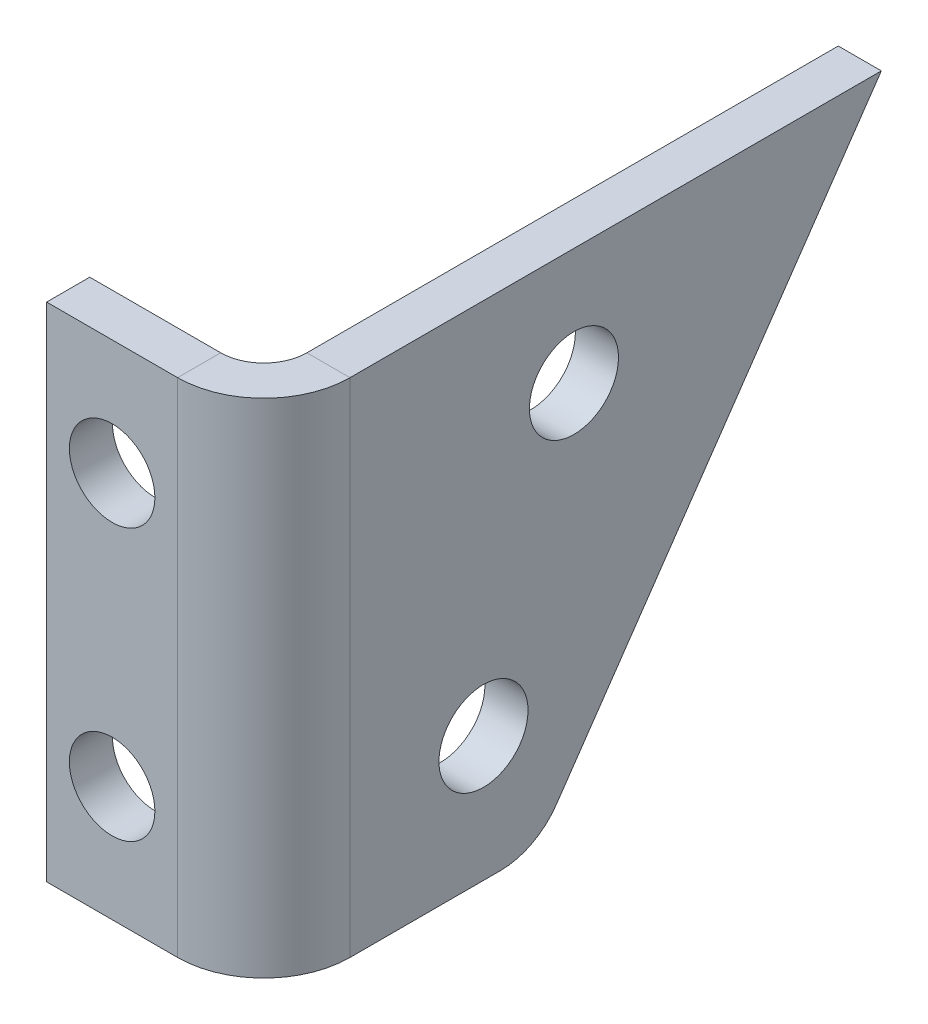
SolidWorks part; units mm, degrees
note: The reader was unsure of these and kept them because the rebuilt part matched: flange length of "Edge-Flange1".
ref_plane "Front Plane" through (0, 0, 0) normal (0, 0, 1) x (1, 0, 0)
ref_plane "Top Plane" through (0, 0, 0) normal (0, 1, 0) x (1, 0, 0)
ref_plane "Right Plane" through (0, 0, 0) normal (1, 0, 0) x (0, 0, -1)
sketch "Sketch1" plane through (0, 0, 0) normal (1, 0, 0) x (0, 0, -1)
  line L0 (71.7184, 2.1678) -> (102.9942, 47.6694)
  line L1 (0, 0) -> (95.6245, 0)
  line L5 (74.7808, 82.752) -> (14.6027, 58.2976)
  line L6 (11.5511, 53.6652) -> (11.5511, 40.2912)
  line L7 (11.5511, 40.2912) -> (48.3501, 40.2912)
  line L8 (50.1591, 38.5003) -> (50.1591, 0)
  line L9 (50.1591, 0) -> (67.5979, 0)
  line L10 (56.6677, 37) -> (96.5316, 37)
  line L11 (48.5511, 46.2861) -> (48.5511, 71.7841)
  arc A0 (67.5979, 0) -> (71.7184, 2.1678) centre (67.5979, 5) ccw
  arc A1 (102.9942, 47.6694) -> (74.7808, 82.752) centre (83.6279, 60.9809) ccw
  arc A2 (14.6027, 58.2976) -> (11.5511, 53.6652) centre (16.551, 53.6928) ccw
  arc A3 (50.1591, 38.5003) -> (48.3501, 40.2912) centre (48.3591, 38.4912) ccw
  circle A4 centre (20.4902, 52.6725) radius 3.15
  circle A5 centre (39.0112, 57.1948) radius 3.15
  circle A6 centre (66.345, 9.2223) radius 3.2825
  circle A7 centre (73.0099, 28.4056) radius 3.2825
  circle A8 centre (83.6279, 42.4814) radius 1.75
  circle A9 centre (102.3808, 60.9809) radius 1.75
  circle A10 centre (83.6279, 79.4804) radius 1.75
  circle A11 centre (83.6279, 60.9809) radius 13.8
  circle A12 centre (65.3817, 60.9809) radius 1.75
  dimension "D3" = 1.8
  dimension "D4" = 23.5
  dimension "D5" = 27.6
  dimension "D6" = 3.5
  dimension "D7" = 6.3
  dimension "D1" = 37
  dimension "D2" = 37
sketch "Sketch2" plane through (0, 0, 0) normal (1, 0, 0) x (0, 0, -1)
  line L8 (50.1591, 38.5003) -> (50.1591, 0) construction
  line L9 (0, 0) -> (95.6245, 0) construction
  line L10 (71.7184, 2.1678) -> (102.9942, 47.6694) construction
  line L11 (56.6677, 37) -> (96.5316, 37) construction
  line L12 (50.1591, 37) -> (50.1591, 0)
  line L13 (50.1591, 0) -> (67.5979, 0)
  line L14 (71.7184, 2.1678) -> (95.6605, 37)
  line L15 (50.1591, 37) -> (95.6605, 37)
  circle A6 centre (73.0099, 28.4056) radius 3.2825 construction
  circle A7 centre (66.345, 9.2223) radius 3.2825 construction
  arc A8 (67.5979, 0) -> (71.7184, 2.1678) centre (67.5979, 5) ccw construction
  circle A9 centre (73.0099, 28.4056) radius 3.2825
  circle A10 centre (66.345, 9.2223) radius 3.2825
  arc A11 (67.5979, 0) -> (71.7184, 2.1678) centre (67.5979, 5) ccw
base flange "Base-Flange1" sketch "Sketch2" thickness 3.175 reverse thickness direction no parameters "D1"=3.175
edge flange "Edge-Flange1" sketch "Sketch5" flange angle 90 flange length 12.825 flange position material inside bend radius 3.175 thickness 3.175 relief rectangular parameters "D6"=10
sketch "Sketch5" plane through (-3.175, 0, -50.1591) normal (0, 0, -1) x (0, -1, 0)
  line L2 (-37, 0) -> (-37, 12.825)
  line L3 (-37, 12.825) -> (0, 12.825)
  line L4 (0, 12.825) -> (0, 0)
  line L5 (0, 0) -> (-37, 0) construction
  line L6 (0, 0) -> (-37, 0)
bend "EdgeBend1" bend radius 3.175 bend angle 90 parameters "D5"=1
sketch "Sketch6" plane through (0, 0, -53.3341) normal (0, 0, -1) x (-1, 0, 0)
  line L0 (6.35, 18.5) -> (16, 18.5) construction
  line L2 (16, 0) -> (16, 37) construction
  line L3 (11.175, 8.5) -> (11.175, 28.5) construction
  line L5 (6.35, 0) -> (6.35, 37) construction
  circle A0 centre (11.175, 28.5) radius 3.15
  circle A1 centre (11.175, 8.5) radius 3.15
  point P9 (11.175, 18.5)
  dimension "D1" = 6.3
extrude "Cut-Extrude1" cut sketch "Sketch6" against normal blind 10 normal cut yes
sketch "Bend-Lines1" [suppressed] plane through (0, 0, 0) normal (0, 1, 0) x (1, 0, 0)
sketch "Bounding-Box1" [suppressed] plane through (0, 0, 0) normal (0, 1, 0) x (1, 0, 0)
sheet metal parameters "Sheet-Metal1" thickness 3.175 parameters "D1"=3.175
flat pattern "Flat-Pattern1" [suppressed]
sketch "Bend-Lines2" plane through (0, 0, 0) normal (0, 1, 0) x (1, 0, 0)
sketch3d "Bounding-Box2" [suppressed]
  line L0 (-17.4389, -5, 0) -> (28.0626, -5, 0) construction
  line L1 (-17.4389, 32, 0) -> (28.0626, 32, 0) construction
  line L2 (-17.4389, -5, 0) -> (-17.4389, 32, 0) construction
  line L3 (28.0626, -5, 0) -> (28.0626, 32, 0) construction
sheet metal parameters "Sheet-Metal4" thickness 3.175 parameters "D1"=3.175
flat pattern "Flat-Pattern1"
sketch "Bend-Lines2" plane through (0, 0, 0) normal (1, 0, 0) x (0, 0, -1)
  line L0 (54.9216, 37) -> (54.9216, 0) construction
  line L1 (54.9216, 37) -> (54.9216, 0) construction
sketch3d "Bounding-Box2" [suppressed]
  line L0 (-23.9139, -5, 0) -> (28.0626, -5, 0) construction
  line L1 (-23.9139, 32, 0) -> (28.0626, 32, 0) construction
  line L2 (-23.9139, -5, 0) -> (-23.9139, 32, 0) construction
  line L3 (28.0626, -5, 0) -> (28.0626, 32, 0) construction
bend of the flat pattern "Flatten-<EdgeBend1>1"
sheet metal parameters "Sheet-Metal5" thickness 3.175 parameters "D1"=3.175
flat pattern "Flat-Pattern1"
sketch "Bend-Lines2" plane through (0, 0, 0) normal (1, 0, 0) x (0, 0, -1)
  line L0 (54.9216, 37) -> (54.9216, 0) construction
  line L1 (54.9216, 37) -> (54.9216, 0) construction
sketch3d "Bounding-Box2" [suppressed]
  line L0 (-23.9139, -5, 0) -> (28.0626, -5, 0) construction
  line L1 (-23.9139, 32, 0) -> (28.0626, 32, 0) construction
  line L2 (-23.9139, -5, 0) -> (-23.9139, 32, 0) construction
  line L3 (28.0626, -5, 0) -> (28.0626, 32, 0) construction
bend of the flat pattern "Flatten-<EdgeBend1>1"
